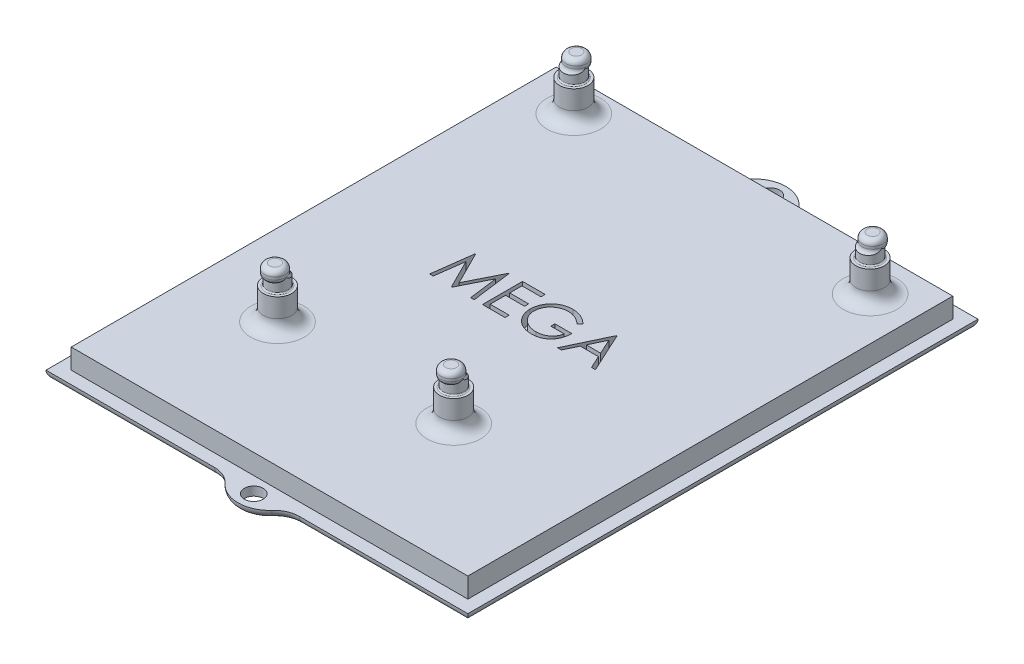
SolidWorks part; units mm, degrees
ref_plane "Front Plane" through (0, 0, 0) normal (0, 0, 1) x (1, 0, 0)
ref_plane "Top Plane" through (0, 0, 0) normal (0, 1, 0) x (1, 0, 0)
ref_plane "Right Plane" through (0, 0, 0) normal (1, 0, 0) x (0, 0, -1)
sketch "Sketch1" plane through (0, 0, 0) normal (0, 1, 0) x (1, 0, 0)
  line L0 (-31.45, 38.45) -> (31.45, 38.45)
  line L5 (-31.45, 38.45) -> (-31.45, -38.45)
  line L6 (-31.45, -38.45) -> (31.45, -38.45)
  line L7 (31.45, 38.45) -> (31.45, -38.45)
  point P11 (-31.45, 0)
  point P12 (0, -38.45)
  dimension "D3" = 76.9
  dimension "D4" = 62.9
extrude "Boss-Extrude1" add sketch "Sketch1" along normal blind 4.575
sketch "Sketch2" plane through (0, 4.575, 0) normal (0, 1, 0) x (1, 0, 0)
  line L0 (9.37, -18.62) -> (9.37, 32.18) construction
  line L1 (24.61, 32.18) -> (9.37, 32.18) construction
  line L2 (9.37, -18.62) -> (-18.57, -18.62) construction
  line L3 (-18.57, -18.62) -> (-18.57, 33.45) construction
  line L4 (0, -38.45) -> (0, 38.45) construction
  line L5 (-31.45, 0) -> (31.45, 0) construction
  line L6 (-18.57, 33.45) -> (-23.65, 33.45) construction
  line L11 (-31.45, 38.45) -> (-31.45, -38.45) construction
  line L12 (-31.45, -38.45) -> (31.45, -38.45) construction
  line L13 (31.45, 38.45) -> (-31.45, 38.45) construction
  line L14 (31.45, -38.45) -> (31.45, 38.45) construction
  circle A4 centre (24.61, 32.18) radius 2.25
  circle A5 centre (9.37, -18.62) radius 2.25
  circle A6 centre (-18.57, -18.62) radius 2.25
  circle A7 centre (-23.65, 33.45) radius 2.25
  point P1 (0, 0)
  dimension "D7" = 4.5
  dimension "D6" = 7.8
  dimension "D8" = 5
  dimension "D1" = 27.94
  dimension "D2" = 15.24
  dimension "D3" = 5.08
  dimension "D4" = 1.27
  dimension "D5" = 50.8
extrude "Boss-Extrude2" add sketch "Sketch2" along normal blind 5
sketch "Sketch7" plane through (0, 0, 0) normal (0, -1, 0) x (1, 0, 0)
  line L8 (-33.45, 40.45) -> (-33.45, -40.45)
  line L9 (-33.45, -40.45) -> (33.45, -40.45)
  line L10 (33.45, -40.45) -> (33.45, 40.45)
  line L11 (33.45, 40.45) -> (-33.45, 40.45)
  line L12 (-33.45, 40.45) -> (-33.45, -40.45)
  line L13 (-33.45, -40.45) -> (33.45, -40.45)
  line L14 (33.45, -40.45) -> (33.45, 40.45)
  line L15 (33.45, 40.45) -> (-33.45, 40.45)
  dimension "D1" = 2
extrude "Boss-Extrude5" add sketch "Sketch7" against normal blind 1.4
sketch "Sketch4" plane through (0, 0, 0) normal (0, 1, 0) x (1, 0, 0)
  line L2 (-6.7082, -40.45) -> (6.7082, -40.45)
  line L3 (-31.45, -38.45) -> (31.45, -38.45) construction
  line L6 (-31.45, -38.45) -> (31.45, -38.45) construction
  line L7 (33.45, -40.45) -> (-33.45, -40.45) construction
  arc A3 (-6.7082, -40.45) -> (-3.7268, -41.7833) centre (-6.7082, -44.45) cw
  arc A4 (-3.7268, -41.7833) -> (3.7268, -41.7833) centre (0, -38.45) ccw
  arc A5 (3.7268, -41.7833) -> (6.7082, -40.45) centre (6.7082, -44.45) cw
  point P6 (0, -38.45)
  dimension "D1" = 5
  dimension "D2" = 4
extrude "Boss-Extrude3" add sketch "Sketch4" along normal blind 1.4
sketch "Sketch8" plane through (0, 1.4, 0) normal (0, 1, 0) x (1, 0, 0)
  line L0 (0, -38.45) -> (0, -43.45) construction
  line L1 (31.45, -38.45) -> (-31.45, -38.45) construction
  arc A0 (-3.7268, -41.7833) -> (3.7268, -41.7833) centre (0, -38.45) ccw construction
  circle A1 centre (0, -40.95) radius 1.5
  dimension "D1" = 3
extrude "Cut-Extrude3" cut sketch "Sketch8" against normal up to next
mirror "Mirror1" about plane through (0, 0, 0) normal (0, 0, 1) of "Cut-Extrude3", "Boss-Extrude3"
sketch "Sketch5" plane through (0, 4.575, 0) normal (0, 1, 0) x (1, 0, 0)
  line L0 (-15, 0) -> (15, 0) construction
  text T0 "MEGA" font "Century Gothic" height in points 24
  point P6 (0, 0)
  dimension "D1" = 30
extrude "Cut-Extrude2" cut sketch "Sketch5" against normal blind 2
fillet "Fillet1" radius 1.4 12 edges at (20.0791, 0, -40.45) (5.0752, 0, -40.7985) (0, 0, -43.45) (-5.0752, 0, -40.7985) (-20.0791, 0, -40.45) (-33.45, 0, 0) (-20.0791, 0, 40.45) (-5.0752, 0, 40.7985) (0, 0, 43.45) (5.0752, 0, 40.7985) (20.0791, 0, 40.45) (33.45, 0, 0)
fillet "Fillet2" radius 2 4 edges at (24.61, 4.575, -29.93) (-23.65, 4.575, -31.2) (9.37, 4.575, 20.87) (-18.57, 4.575, 20.87)
sketch "Sketch9" plane through (0, 9.575, 0) normal (0, 1, 0) x (1, 0, 0)
  circle A0 centre (-18.57, -18.62) radius 1.65
  circle A1 centre (9.37, -18.62) radius 1.65
  circle A2 centre (-23.65, 33.45) radius 1.65
  circle A3 centre (24.61, 32.18) radius 1.65
  dimension "D1" = 3.3
extrude "Boss-Extrude6" add sketch "Sketch9" along normal blind 1.3
sketch "Sketch10" plane through (0, 10.875, 0) normal (0, 1, 0) x (1, 0, 0)
  circle A13 centre (9.37, -19.02) radius 1.65
  circle A14 centre (9.37, -18.62) radius 1.65 construction
  circle A15 centre (24.61, 32.58) radius 1.65
  circle A16 centre (-18.57, -19.02) radius 1.65
  circle A17 centre (-23.65, 33.85) radius 1.65
  circle A19 centre (-23.65, 33.45) radius 1.65 construction
  circle A20 centre (24.61, 32.18) radius 1.65 construction
  circle A21 centre (-18.57, -18.62) radius 1.65 construction
  point P4 (-23.65, 33.45)
  point P5 (9.37, -18.62)
  point P6 (-18.57, -18.62)
  point P7 (24.61, 32.18)
  point P14 (0, 0)
  point P15 (0, 0)
  point P20 (0, 0)
  dimension "D1" = 0.4
  dimension "D2" = 0.4
  dimension "D3" = 0.4
  dimension "D4" = 0.4
extrude "Boss-Extrude8" add sketch "Sketch10" along normal blind 2
fillet "Fillet8" radius 0.8 8 edges at (24.61, 12.875, -30.93) (-18.57, 12.875, 20.67) (9.37, 12.875, 20.67) (24.61, 10.875, -34.23) (-23.65, 10.875, -35.5) (-23.65, 12.875, -32.2) (-18.57, 10.875, 20.67) (9.37, 10.875, 20.67)
fillet "Fillet9" radius 0.8 4 edges at (24.61, 10.875, -30.93) (-23.65, 10.875, -32.2) (-18.57, 10.875, 17.37) (9.37, 10.875, 17.37)
fillet "Fillet10" radius 0.2 4 edges at (-23.65, 9.575, -31.8) (24.61, 9.575, -30.53) (-18.57, 9.575, 20.27) (9.37, 9.575, 20.27)
